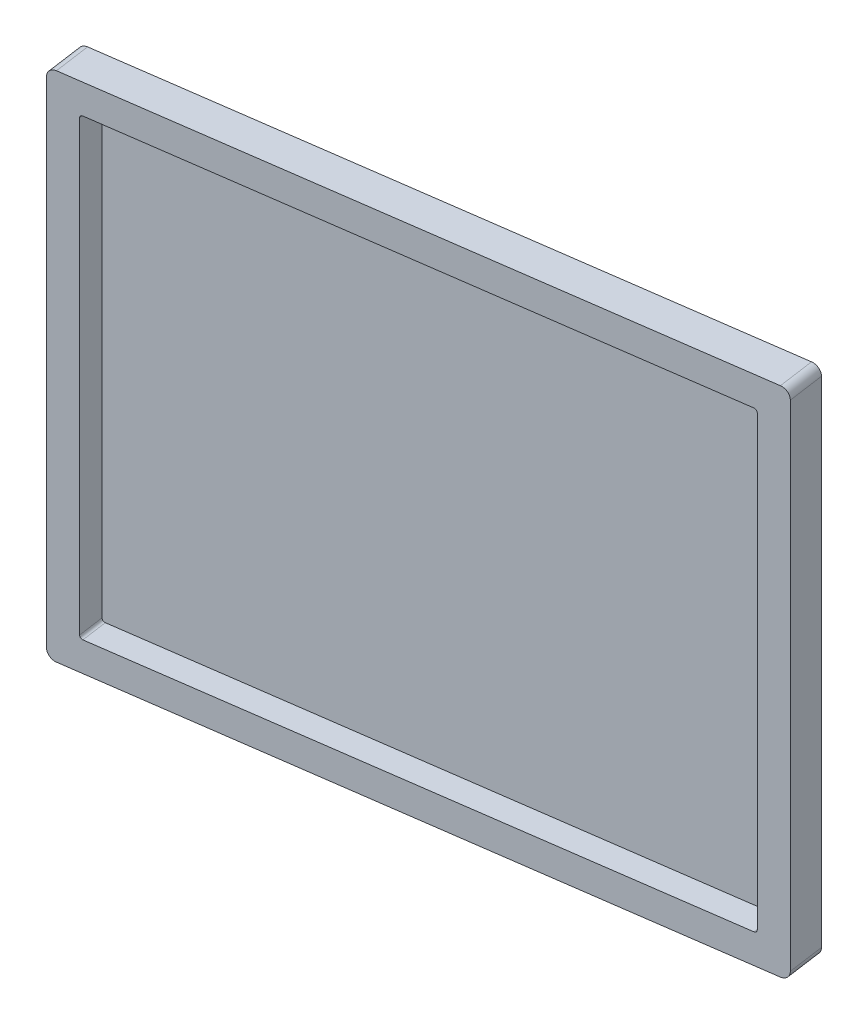
SolidWorks part; units mm, degrees
material "6061-T6 (SS)"
ref_plane "Front Plane" through (0, 0, 0) normal (0, 0, 1) x (1, 0, 0)
ref_plane "Top Plane" through (0, 0, 0) normal (0, 1, 0) x (1, 0, 0)
ref_plane "Right Plane" through (0, 0, 0) normal (1, 0, 0) x (0, 0, -1)
sketch "Extrude sketch 1" plane through (0, 0, 0) normal (0, 0, 1) x (1, 0, 0)
  line L0 (219, 175) -> (-219, 175)
  line L1 (-225, 169) -> (-225, -169)
  line L2 (-219, -175) -> (219, -175)
  line L3 (225, -169) -> (225, 169)
  line L4 (203, 155) -> (-203, 155)
  line L5 (-205, 153) -> (-205, -153)
  line L6 (-203, -155) -> (203, -155)
  line L7 (205, -153) -> (205, 153)
  arc A0 (-219, 175) -> (-225, 169) centre (-219, 169) ccw
  arc A1 (-225, -169) -> (-219, -175) centre (-219, -169) ccw
  arc A2 (219, -175) -> (225, -169) centre (219, -169) ccw
  arc A3 (225, 169) -> (219, 175) centre (219, 169) ccw
  arc A4 (-203, 155) -> (-205, 153) centre (-203, 153) ccw
  arc A5 (-205, -153) -> (-203, -155) centre (-203, -153) ccw
  arc A6 (203, -155) -> (205, -153) centre (203, -153) ccw
  arc A7 (205, 153) -> (203, 155) centre (203, 153) ccw
  dimension "D1" = 6
  dimension "D2" = 2
  dimension "D3" = 20
  dimension "D4" = 430
  dimension "D5" = 450
  dimension "D6" = 20
  dimension "D7" = 330
  dimension "D8" = 350
extrude "Extrude 1" add sketch "Extrude sketch 1" along normal blind 25 from offset 12.5 separate body offset against normal yes
move or copy body "Extrude rotate 1" bodies to move or copy 101 copy no rotation origin (0, 0, 0) rotation axis (0, 1, 0) rotation angle 8
move or copy body "Extrude place 1" bodies to move or copy 102 copy no translate (588.9293, 0, 623.6923) parameters "D1"=588.9293, "D2"=0, "D3"=623.6923
sketch "Extrude sketch 2" plane through (0, 0, 0) normal (0, 0, 1) x (1, 0, 0)
  line L0 (-205, -155) -> (205, -155)
  line L1 (205, -155) -> (205, 155)
  line L2 (205, 155) -> (-205, 155)
  line L3 (-205, 155) -> (-205, -155)
  dimension "D1" = 410
  dimension "D2" = 310
extrude "Extrude 2" add sketch "Extrude sketch 2" along normal blind 3 from offset 8.5 separate body offset against normal yes
move or copy body "Extrude rotate 2" bodies to move or copy 104 copy no rotation origin (0, 0, 0) rotation axis (0, 1, 0) rotation angle 8
move or copy body "Extrude place 2" bodies to move or copy 105 copy no translate (588.9293, 0, 623.6923) parameters "D1"=588.9293, "D2"=0, "D3"=623.6923
sketch "Extrude sketch 3" plane through (0, 0, 0) normal (0, 0, 1) x (1, 0, 0)
  line L0 (60, -40) -> (140, -40)
  line L1 (140, -40) -> (140, 40)
  line L2 (140, 40) -> (60, 40)
  line L3 (60, 40) -> (60, -40)
  dimension "D1" = 80
extrude "Extrude 3" add sketch "Extrude sketch 3" along normal blind 22 from offset 30.5 separate body offset against normal yes
move or copy body "Extrude rotate 3" bodies to move or copy 107 copy no rotation origin (0, 0, 0) rotation axis (0, 1, 0) rotation angle 8
move or copy body "Extrude place 3" bodies to move or copy 108 copy no translate (588.9293, 0, 623.6923) parameters "D1"=588.9293, "D2"=0, "D3"=623.6923
combine bodies "Combine (weld / assembly of features)" operation type add bodies to combine 103 109 106
